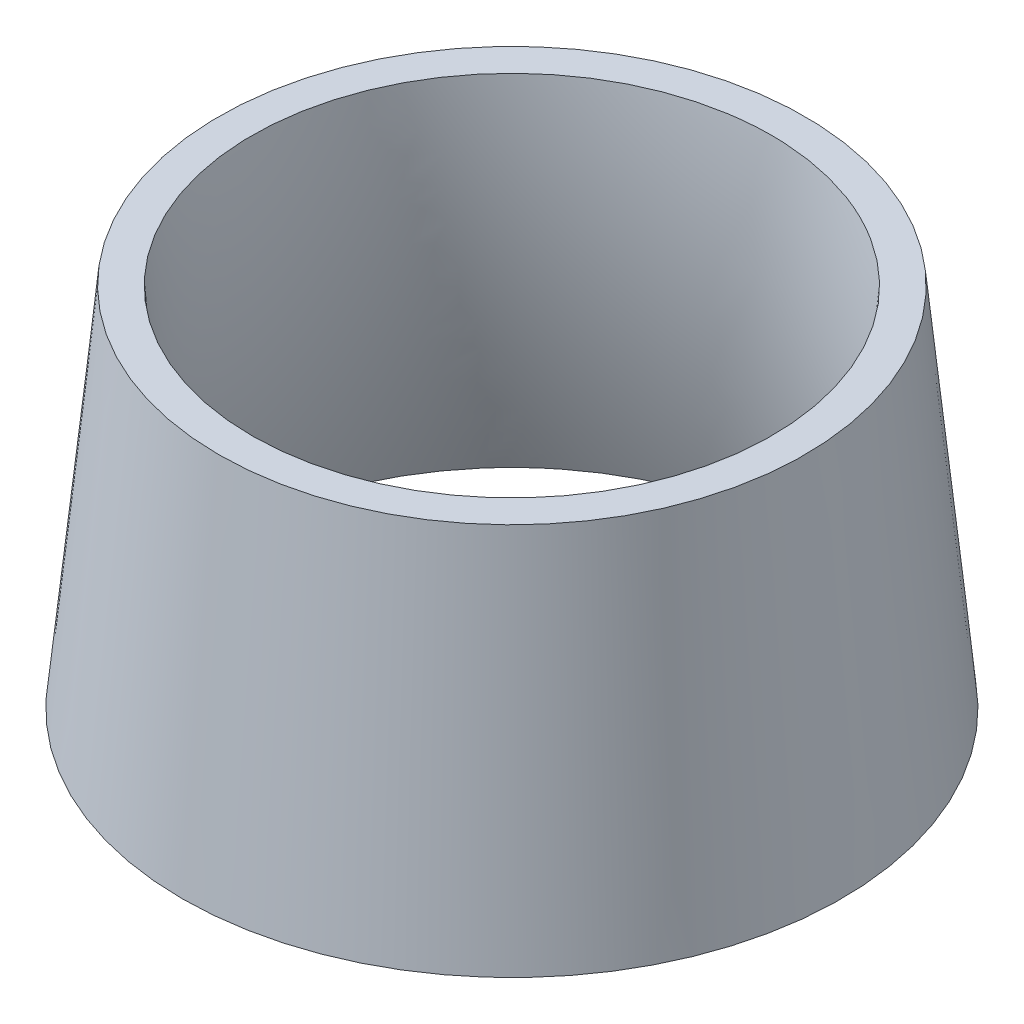
SolidWorks part; units mm, degrees
ref_plane "Front" through (0, 0, 0) normal (0, 0, 1) x (1, 0, 0)
ref_plane "Top" through (0, 0, 0) normal (0, 1, 0) x (1, 0, 0)
ref_plane "Right" through (0, 0, 0) normal (1, 0, 0) x (0, 0, -1)
sketch "Sketch1" plane through (0, 0, 0) normal (0, 1, 0) x (1, 0, 0)
  circle A0 centre (0, 0) radius 57.15
  circle A1 centre (0, 0) radius 51.181
  dimension "D1" = 114.3
  dimension "D2" = 102.362
ref_plane "Plane1" through (0, 63.5, 0) normal (0, 1, 0) x (1, 0, 0)
sketch "Sketch2" plane through (0, 63.5, 0) normal (0, 1, 0) x (1, 0, 0)
  circle A0 centre (0, 0) radius 50.8
  circle A1 centre (0, 0) radius 45.085
  dimension "D1" = 101.6
  dimension "D2" = 90.17
loft "Loft1" add section "Sketch2" section "Sketch1" connector at (-50.4269, 63.5, 6.1452) connector at (-56.131, 0, 10.7441)
loft "Cut-Loft1" cut section "Sketch2<3>" section "Sketch1<3>" connector at (-9.0594, 63.5, 44.1654) connector at (25.4697, 0, 44.3936)
sketch "Sketch2<3>" plane through (0, 63.5, 0) normal (0, 1, 0) x (1, 0, 0) same geometry as "Sketch2"
sketch "Sketch1<3>" plane through (0, 0, 0) normal (0, 1, 0) x (1, 0, 0) same geometry as "Sketch1"
